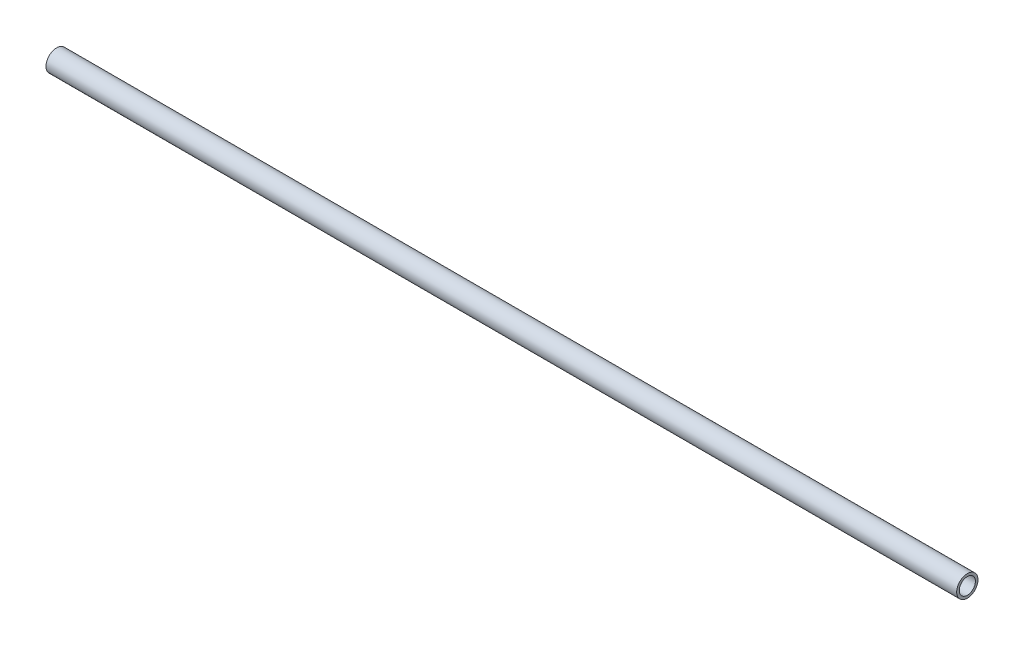
SolidWorks part; units mm, degrees
ref_plane "Front Plane" through (0, 0, 0) normal (0, 0, 1) x (1, 0, 0)
ref_plane "Top Plane" through (0, 0, 0) normal (0, 1, 0) x (1, 0, 0)
ref_plane "Right Plane" through (0, 0, 0) normal (1, 0, 0) x (0, 0, -1)
ref_axis "Axis1" through (-4.5, 0, 0) along (1, 0, 0)
sketch "Sketch1" plane through (0, 0, 0) normal (1, 0, 0) x (0, 0, -1)
  circle A0 centre (0, 0) radius 0.8001
  circle A1 centre (0, 0) radius 1.0541
  dimension "D1" = 1.6002
  dimension "D2" = 2.1082
extrude "Boss-Extrude1" add sketch "Sketch1" along normal blind 90
sketch "Sketch2" plane through (0, 0, 0) normal (-1, 0, 0) x (0, 0, 1)
  line L0 (0, 0) -> (0, 0.6106) construction
  line L2 (-0.304, 0.6106) -> (-0.304, 1.0992)
  line L3 (-0.304, 1.0992) -> (0.304, 1.0992)
  line L4 (0.304, 1.0992) -> (0.304, 0.6106)
  arc A0 (-0.304, 0.6106) -> (0.304, 0.6106) centre (0, 0.6106) ccw
  dimension "D1" = 0.608
extrude "Cut-Extrude1" [suppressed] cut sketch "Sketch2" against normal blind 1
sketch "Sketch3" plane through (0, 0, 0) normal (0, 0, 1) x (1, 0, 0)
  circle A0 centre (1.6674, 0) radius 0.7938
  dimension "D1" = 1.5875
extrude "Cut-Extrude2" cut sketch "Sketch3" against normal blind 10
equation "\"Do\"=8.5mm"
equation "\"Lo\"=10"
equation "\"screw_diam\" = 3.5mm"
equation "\"wheel_Do\"=12.5mm"
equation "\"wheel_thickness\"=4mm"
equation "\"Collet_diameter\"=4.3"
equation "\"clearance\"= 0.5mm"
equation "\"handle_body_width\" = 10mm"
equation "\"finger_diameter\"=35"
equation "\"collet_lid_diameter\"=10"
equation "\"screw_cap_diam\"=5.15"
equation "\"handle_thickness\"=12.5mm"
equation "\"post_hole_diam\"=2"
equation "\"roll_rod_diam\"= 6.5 "
equation "\"roll_rod_length\"=6.6"
equation "\"disc_diam\"=5"
equation "\"disc_width\"=1.5"
equation "\"arm_width\"=5"
equation "\"arm_thickness\"=4.5"
equation "\"wheel_total_diam\"=30"
equation "\"spring_diam\"=4.1"
equation "\"collet_length\" = 18.75mm"
equation "\"tip_length\" = 40mm"
equation "\"cable_tube_OD\"=0.508"
equation "\"D1@Sketch2\"=\"cable_tube_OD\"+0.1"
